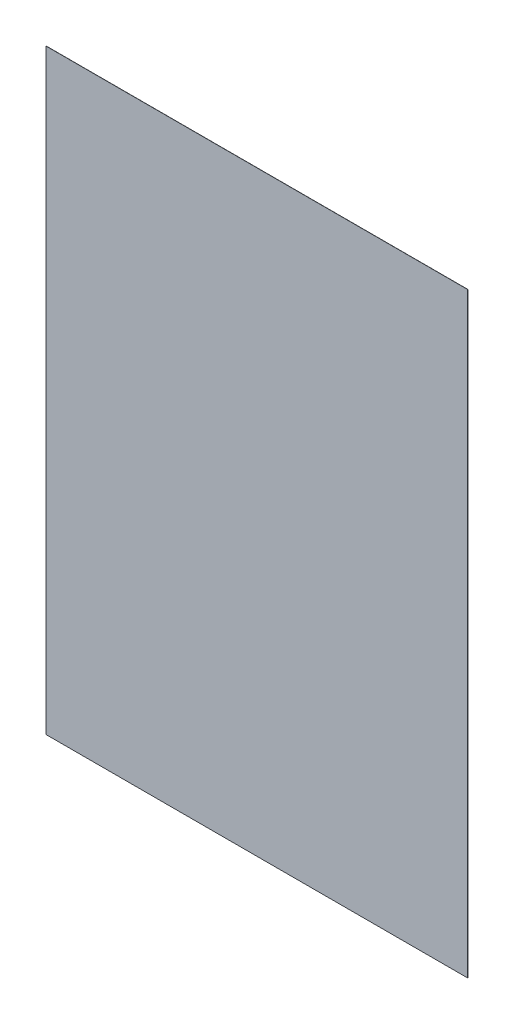
SolidWorks part; units mm, degrees
ref_plane "前视基准面" through (0, 0, 0) normal (0, 0, 1) x (1, 0, 0)
ref_plane "上视基准面" through (0, 0, 0) normal (0, 1, 0) x (1, 0, 0)
ref_plane "右视基准面" through (0, 0, 0) normal (1, 0, 0) x (0, 0, -1)
sketch "草图1" plane through (0, 0, 0) normal (0, 0, 1) x (1, 0, 0)
  line L1 (0, 0) -> (210, 0)
  line L2 (0, 0) -> (0, 297)
  line L3 (0, 297) -> (210, 297)
  line L4 (210, 0) -> (210, 297)
  dimension "D1" = 297
  dimension "D2" = 210
extrude "凸台-拉伸1" add sketch "草图1" along normal blind 0.1
